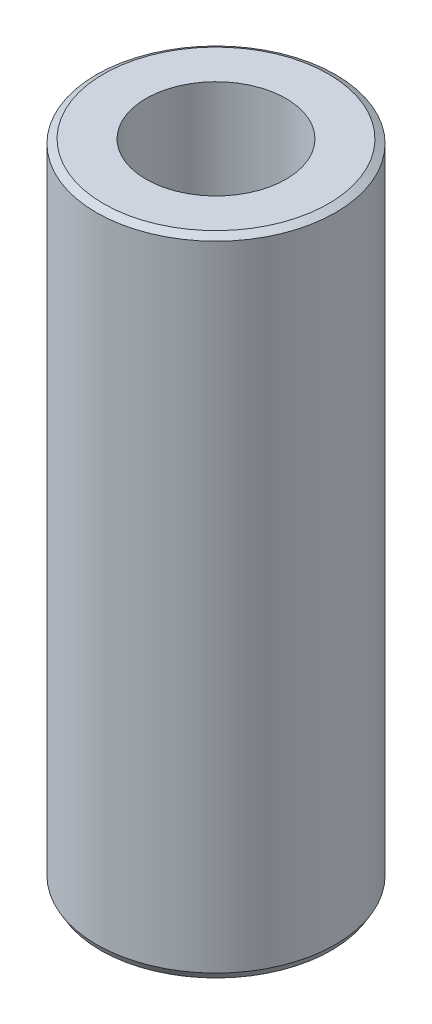
SolidWorks part; units mm, degrees
ref_plane "Front Plane" through (0, 0, 0) normal (0, 0, 1) x (1, 0, 0)
ref_plane "Top Plane" through (0, 0, 0) normal (0, 1, 0) x (1, 0, 0)
ref_plane "Right Plane" through (0, 0, 0) normal (1, 0, 0) x (0, 0, -1)
sketch "Sketch1" plane through (0, 0, 0) normal (0, 1, 0) x (1, 0, 0)
  circle A0 centre (0, 0) radius 20
  dimension "SHAFT_OD" = 40
extrude "Boss-Extrude1" add sketch "Sketch1" along normal blind 107.914
sketch "Sketch2" plane through (0, 0, 0) normal (0, 1, 0) x (1, 0, 0)
  circle A0 centre (0, 0) radius 11.7107
  dimension "BORE_D" = 23.4215
extrude "Cut-Extrude1" cut sketch "Sketch2" along normal through all
chamfer "Chamfer1" distance 0.6893 angle 60 2 edges at (0, 107.914, 20) (0, 0, 20) first distance on face at (0, 107.914, 20) first distance on face at (0, 0, 11.7107)
